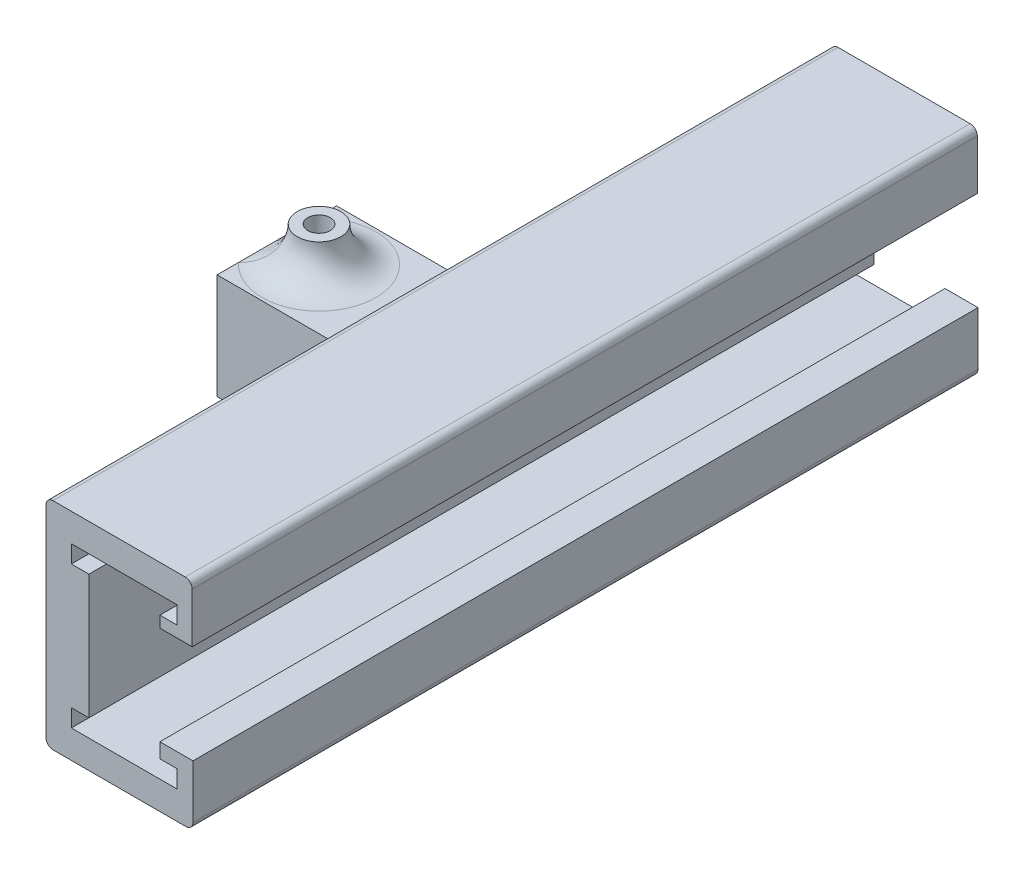
SolidWorks part; units mm, degrees
ref_plane "Front Plane" through (0, 0, 0) normal (0, 0, 1) x (1, 0, 0)
ref_plane "Top Plane" through (0, 0, 0) normal (0, 1, 0) x (1, 0, 0)
ref_plane "Right Plane" through (0, 0, 0) normal (1, 0, 0) x (0, 0, -1)
sketch "Sketch1" plane through (0, 0, 0) normal (0, 0, 1) x (1, 0, 0)
  line L0 (0, 0) -> (0, -2)
  line L1 (10.1, -2) -> (12.9, -2)
  line L2 (14.1, -0.8) -> (14.1, 4.1)
  line L3 (0, 0) -> (-2.1, 0)
  line L4 (-2.1, 0) -> (-2.1, 2.1)
  line L5 (-2.1, 2.1) -> (12.1, 2.1)
  line L6 (12.1, 2.1) -> (12.1, 0)
  line L7 (12.1, 0) -> (10.1, 0)
  line L8 (10.1, 0) -> (10.1, -2)
  line L9 (14.1, 4.1) -> (-4.1, 4.1)
  line L10 (-4.1, 4.1) -> (-4.1, -22.6)
  line L11 (0, -2) -> (0, -18.5)
  line L12 (0, -18.5) -> (-2.1, -18.5)
  line L13 (-2.1, -18.5) -> (-2.1, -20.6)
  line L14 (-2.1, -20.6) -> (12.2, -20.6)
  line L15 (12.2, -20.6) -> (12.2, -18.5)
  line L16 (12.2, -18.5) -> (10.1, -18.5)
  line L17 (10.1, -18.5) -> (10.1, -2)
  line L18 (-4.1, -22.6) -> (14.2, -22.6)
  line L19 (14.2, -22.6) -> (14.2, -17.7)
  line L20 (10.1, -16.5) -> (13, -16.5)
  line L21 (16.1, -2) -> (16.1, -1.9919)
  arc A0 (14.2, -17.7) -> (13, -16.5) centre (13, -17.7) ccw
  arc A1 (14.1, -0.8) -> (12.9, -2) centre (12.9, -0.8) cw
  point P27 (14.2, -16.5)
  dimension "D18" = 1.2
  dimension "D1" = 14.2
  dimension "D2" = 10.1
  dimension "D3" = 2.1
  dimension "D4" = 2.1
  dimension "D5" = 2
  dimension "D6" = 2
  dimension "D7" = 2
  dimension "D8" = 2
  dimension "D9" = 2
  dimension "D10" = 2
  dimension "D11" = 2.1
  dimension "D12" = 2.1
  dimension "D13" = 2.1
  dimension "D14" = 14.3
  dimension "D15" = 2
  dimension "D16" = 16.5
  dimension "D17" = 2
extrude "Boss-Extrude1" add sketch "Sketch1" along normal blind 85 contours L1 L21 L2 L9 L10 L18 L19 L20 L17 L16 L15 L14 L13 L12 L11 L0 L3 L4 L5 L6 L7 L8 region at (-0.3237, -1, 0)
sketch "Sketch2" plane through (14.1, 0, 0) normal (1, 0, 0) x (0, 0, -1)
  line L1 (-85, 4.1) -> (0, 4.1)
  line L2 (-85, 4.1) -> (-85, -11.9)
  line L3 (-85, -11.9) -> (0, -11.9)
  line L4 (0, 4.1) -> (0, -11.9)
  line L5 (0, -0.8) -> (0, 4.1) construction
  dimension "D1" = 16
extrude "Boss-Extrude2" add sketch "Sketch2" against normal blind 1.8
sketch "Sketch3" plane through (-4.1, 0, 0) normal (-1, 0, 0) x (0, 0, 1)
  line L0 (85, -22.6) -> (0, -22.6) construction
  line L1 (0, 4.1) -> (0, -22.6) construction
  circle A0 centre (42.5, -9.25) radius 4
  point P5 (42.5, -22.6)
  point P8 (0, -9.25)
  dimension "D1" = 8
extrude "Cut-Extrude1" cut sketch "Sketch3" against normal blind 10 contours A0 | A0 region at (-4.1, -9.25, 42.5)
sketch "Sketch4" plane through (0, 4.1, 0) normal (0, 1, 0) x (1, 0, 0)
  line L0 (14.1, 0) -> (-4.1, 0) construction
  line L1 (-4.1, -85) -> (-4.1, 0) construction
  line L2 (14.1, -85) -> (-4.1, -85) construction
  line L3 (0.9, -5) -> (0.9, -80) construction
  circle A0 centre (0.9, -5) radius 3
  circle A1 centre (0.9, -80) radius 3
  circle A2 centre (0.9, -5) radius 5
  circle A3 centre (0.9, -80) radius 5
  dimension "D1" = 6
  dimension "D2" = 6
  dimension "D3" = 2
extrude "Boss-Extrude3" add sketch "Sketch4" along normal blind 2
sketch "Sketch5" plane through (0, 4.1, 0) normal (0, 1, 0) x (1, 0, 0)
  line L0 (13.1, -40.3) -> (-0.9, -40.3)
  line L1 (-0.9, -40.3) -> (-0.9, -42.3)
  line L2 (-0.9, -42.3) -> (1.1, -42.3)
  line L3 (1.1, -42.3) -> (1.1, -46.8)
  line L4 (1.1, -46.8) -> (11.1, -46.8)
  line L5 (11.1, -46.8) -> (11.1, -42.3)
  line L6 (11.1, -42.3) -> (13.1, -42.3)
  line L7 (13.1, -42.3) -> (13.1, -40.3)
  line L8 (14.1, -85) -> (14.1, 0) construction
  line L9 (14.1, -85) -> (0.9, -85) construction
  dimension "D1" = 85
  dimension "D2" = 85
  dimension "D3" = 1
  dimension "D4" = 3
  dimension "D5" = 13
  dimension "D6" = 15
  dimension "D7" = 38.2
  dimension "D8" = 42.7
  dimension "D9" = 42.7
  dimension "D10" = 44.7
extrude "Boss-Extrude4" add sketch "Sketch5" along normal blind 50
sketch "Sketch6" plane through (11.1, 0, 0) normal (1, 0, 0) x (0, 0, -1)
  line L0 (-46.8, 54.1) -> (-46.8, 4.1) construction
  line L1 (-46.8, 54.1) -> (-46.8, 4.1)
  line L2 (-44.8, 4.1) -> (-46.8, 4.1)
  line L3 (-44.8, 6.5) -> (-44.8, 5.6)
  line L4 (-44.8, 5.6) -> (-46.1454, 5.2861)
  line L5 (-46.1454, 4.4139) -> (-44.8, 4.1)
  line L6 (-85, 4.1) -> (0, 4.1) construction
  line L8 (-46.3, 4.6087) -> (-46.3, 5.0913)
  line L9 (-44.8, 6.5) -> (-46.1454, 6.8139)
  line L10 (-46.3, 7.0087) -> (-46.3, 7.4913)
  line L11 (-46.1454, 7.6861) -> (-44.8, 8)
  line L12 (-44.8, 8.9) -> (-46.1454, 9.2139)
  line L13 (-46.3, 9.4087) -> (-46.3, 9.8913)
  line L14 (-46.1454, 10.0861) -> (-44.8, 10.4)
  line L15 (-44.8, 8.9) -> (-44.8, 8)
  line L16 (-44.8, 11.3) -> (-46.1454, 11.6139)
  line L17 (-46.3, 11.8087) -> (-46.3, 12.2913)
  line L18 (-46.1454, 12.4861) -> (-44.8, 12.8)
  line L19 (-44.8, 11.3) -> (-44.8, 10.4)
  line L20 (-44.8, 13.7) -> (-46.1454, 14.0139)
  line L21 (-46.3, 14.2087) -> (-46.3, 14.6913)
  line L22 (-46.1454, 14.8861) -> (-44.8, 15.2)
  line L23 (-44.8, 13.7) -> (-44.8, 12.8)
  line L24 (-44.8, 16.1) -> (-46.1454, 16.4139)
  line L25 (-46.3, 16.6087) -> (-46.3, 17.0913)
  line L26 (-46.1454, 17.2861) -> (-44.8, 17.6)
  line L27 (-44.8, 16.1) -> (-44.8, 15.2)
  line L28 (-44.8, 18.5) -> (-46.1454, 18.8139)
  line L29 (-46.3, 19.0087) -> (-46.3, 19.4913)
  line L30 (-46.1454, 19.6861) -> (-44.8, 20)
  line L31 (-44.8, 18.5) -> (-44.8, 17.6)
  line L32 (-44.8, 20.9) -> (-46.1454, 21.2139)
  line L33 (-46.3, 21.4087) -> (-46.3, 21.8913)
  line L34 (-46.1454, 22.0861) -> (-44.8, 22.4)
  line L35 (-44.8, 20.9) -> (-44.8, 20)
  line L36 (-44.8, 23.3) -> (-46.1454, 23.6139)
  line L37 (-46.3, 23.8087) -> (-46.3, 24.2913)
  line L38 (-46.1454, 24.4861) -> (-44.8, 24.8)
  line L39 (-44.8, 23.3) -> (-44.8, 22.4)
  line L40 (-44.8, 25.7) -> (-46.1454, 26.0139)
  line L41 (-46.3, 26.2087) -> (-46.3, 26.6913)
  line L42 (-46.1454, 26.8861) -> (-44.8, 27.2)
  line L43 (-44.8, 25.7) -> (-44.8, 24.8)
  line L44 (-44.8, 28.1) -> (-46.1454, 28.4139)
  line L45 (-46.3, 28.6087) -> (-46.3, 29.0913)
  line L46 (-46.1454, 29.2861) -> (-44.8, 29.6)
  line L47 (-44.8, 28.1) -> (-44.8, 27.2)
  line L48 (-44.8, 30.5) -> (-46.1454, 30.8139)
  line L49 (-46.3, 31.0087) -> (-46.3, 31.4913)
  line L50 (-46.1454, 31.6861) -> (-44.8, 32)
  line L51 (-44.8, 30.5) -> (-44.8, 29.6)
  line L52 (-44.8, 32.9) -> (-46.1454, 33.2139)
  line L53 (-46.3, 33.4087) -> (-46.3, 33.8913)
  line L54 (-46.1454, 34.0861) -> (-44.8, 34.4)
  line L55 (-44.8, 32.9) -> (-44.8, 32)
  line L56 (-44.8, 35.3) -> (-46.1454, 35.6139)
  line L57 (-46.3, 35.8087) -> (-46.3, 36.2913)
  line L58 (-46.1454, 36.4861) -> (-44.8, 36.8)
  line L59 (-44.8, 35.3) -> (-44.8, 34.4)
  line L60 (-44.8, 37.7) -> (-46.1454, 38.0139)
  line L61 (-46.3, 38.2087) -> (-46.3, 38.6913)
  line L62 (-46.1454, 38.8861) -> (-44.8, 39.2)
  line L63 (-44.8, 37.7) -> (-44.8, 36.8)
  line L64 (-44.8, 40.1) -> (-46.1454, 40.4139)
  line L65 (-46.3, 40.6087) -> (-46.3, 41.0913)
  line L66 (-46.1454, 41.2861) -> (-44.8, 41.6)
  line L67 (-44.8, 40.1) -> (-44.8, 39.2)
  line L68 (-44.8, 42.5) -> (-46.1454, 42.8139)
  line L69 (-46.3, 43.0087) -> (-46.3, 43.4913)
  line L70 (-46.1454, 43.6861) -> (-44.8, 44)
  line L71 (-44.8, 42.5) -> (-44.8, 41.6)
  line L72 (-44.8, 44.9) -> (-46.1454, 45.2139)
  line L73 (-46.3, 45.4087) -> (-46.3, 45.8913)
  line L74 (-46.1454, 46.0861) -> (-44.8, 46.4)
  line L75 (-44.8, 44.9) -> (-44.8, 44)
  line L76 (-44.8, 47.3) -> (-46.1454, 47.6139)
  line L77 (-46.3, 47.8087) -> (-46.3, 48.2913)
  line L78 (-46.1454, 48.4861) -> (-44.8, 48.8)
  line L79 (-44.8, 47.3) -> (-44.8, 46.4)
  line L80 (-44.8, 49.7) -> (-46.1454, 50.0139)
  line L81 (-46.3, 50.2087) -> (-46.3, 50.6913)
  line L82 (-46.1454, 50.8861) -> (-44.8, 51.2)
  line L83 (-44.8, 49.7) -> (-44.8, 48.8)
  line L84 (-44.8, 52.1) -> (-46.1454, 52.4139)
  line L85 (-46.3, 52.6087) -> (-46.3, 53.0913)
  line L86 (-46.1454, 53.2861) -> (-44.8, 53.6)
  line L87 (-44.8, 52.1) -> (-44.8, 51.2)
  line L88 (-46.8, 4.1) -> (-42.3, 4.1) construction
  line L89 (-42.3, 54.1) -> (-42.3, 4.1) construction
  line L91 (-44.8, 54.1) -> (-44.8, 53.6)
  line L92 (-46.8, 54.1) -> (-44.8, 54.1)
  line L93 (-46.8, 54.1) -> (-42.3, 54.1) construction
  line L95 (-44.8, 54.5) -> (-46.1454, 54.8139) [skipped]
  line L96 (-46.3, 55.0087) -> (-46.3, 55.4913) [skipped]
  line L97 (-46.1454, 55.6861) -> (-44.8, 56) [skipped]
  spline S0 degree 2 poles (-46.1454, 4.4139) (-46.2906, 4.4575) (-46.3, 4.6087) knots 0 0 0 1 1 1
  spline S1 degree 2 poles (-46.3, 5.0913) (-46.2906, 5.2425) (-46.1454, 5.2861) knots 0 0 0 1 1 1
  spline S2 degree 2 poles (-46.1454, 6.8139) (-46.2906, 6.8575) (-46.3, 7.0087) knots 0 0 0 1 1 1
  spline S3 degree 2 poles (-46.3, 7.4913) (-46.2906, 7.6425) (-46.1454, 7.6861) knots 0 0 0 1 1 1
  spline S4 degree 2 poles (-46.1454, 9.2139) (-46.2906, 9.2575) (-46.3, 9.4087) knots 0 0 0 1 1 1
  spline S5 degree 2 poles (-46.3, 9.8913) (-46.2906, 10.0425) (-46.1454, 10.0861) knots 0 0 0 1 1 1
  spline S6 degree 2 poles (-46.1454, 11.6139) (-46.2906, 11.6575) (-46.3, 11.8087) knots 0 0 0 1 1 1
  spline S7 degree 2 poles (-46.3, 12.2913) (-46.2906, 12.4425) (-46.1454, 12.4861) knots 0 0 0 1 1 1
  spline S8 degree 2 poles (-46.1454, 14.0139) (-46.2906, 14.0575) (-46.3, 14.2087) knots 0 0 0 1 1 1
  spline S9 degree 2 poles (-46.3, 14.6913) (-46.2906, 14.8425) (-46.1454, 14.8861) knots 0 0 0 1 1 1
  spline S10 degree 2 poles (-46.1454, 16.4139) (-46.2906, 16.4575) (-46.3, 16.6087) knots 0 0 0 1 1 1
  spline S11 degree 2 poles (-46.3, 17.0913) (-46.2906, 17.2425) (-46.1454, 17.2861) knots 0 0 0 1 1 1
  spline S12 degree 2 poles (-46.1454, 18.8139) (-46.2906, 18.8575) (-46.3, 19.0087) knots 0 0 0 1 1 1
  spline S13 degree 2 poles (-46.3, 19.4913) (-46.2906, 19.6425) (-46.1454, 19.6861) knots 0 0 0 1 1 1
  spline S14 degree 2 poles (-46.1454, 21.2139) (-46.2906, 21.2575) (-46.3, 21.4087) knots 0 0 0 1 1 1
  spline S15 degree 2 poles (-46.3, 21.8913) (-46.2906, 22.0425) (-46.1454, 22.0861) knots 0 0 0 1 1 1
  spline S16 degree 2 poles (-46.1454, 23.6139) (-46.2906, 23.6575) (-46.3, 23.8087) knots 0 0 0 1 1 1
  spline S17 degree 2 poles (-46.3, 24.2913) (-46.2906, 24.4425) (-46.1454, 24.4861) knots 0 0 0 1 1 1
  spline S18 degree 2 poles (-46.1454, 26.0139) (-46.2906, 26.0575) (-46.3, 26.2087) knots 0 0 0 1 1 1
  spline S19 degree 2 poles (-46.3, 26.6913) (-46.2906, 26.8425) (-46.1454, 26.8861) knots 0 0 0 1 1 1
  spline S20 degree 2 poles (-46.1454, 28.4139) (-46.2906, 28.4575) (-46.3, 28.6087) knots 0 0 0 1 1 1
  spline S21 degree 2 poles (-46.3, 29.0913) (-46.2906, 29.2425) (-46.1454, 29.2861) knots 0 0 0 1 1 1
  spline S22 degree 3 poles (-46.1454, 30.8139) (-46.2422, 30.8429) (-46.2937, 30.9079) (-46.3, 31.0087) knots 0 0 0 0 1 1 1 1
  spline S23 degree 2 poles (-46.3, 31.4913) (-46.2906, 31.6425) (-46.1454, 31.6861) knots 0 0 0 1 1 1
  spline S24 degree 2 poles (-46.1454, 33.2139) (-46.2906, 33.2575) (-46.3, 33.4087) knots 0 0 0 1 1 1
  spline S25 degree 2 poles (-46.3, 33.8913) (-46.2906, 34.0425) (-46.1454, 34.0861) knots 0 0 0 1 1 1
  spline S26 degree 2 poles (-46.1454, 35.6139) (-46.2906, 35.6575) (-46.3, 35.8087) knots 0 0 0 1 1 1
  spline S27 degree 3 poles (-46.3, 36.2913) (-46.2937, 36.3921) (-46.2422, 36.4571) (-46.1454, 36.4861) knots 0 0 0 0 1 1 1 1
  spline S28 degree 2 poles (-46.1454, 38.0139) (-46.2906, 38.0575) (-46.3, 38.2087) knots 0 0 0 1 1 1
  spline S29 degree 2 poles (-46.3, 38.6913) (-46.2906, 38.8425) (-46.1454, 38.8861) knots 0 0 0 1 1 1
  spline S30 degree 2 poles (-46.1454, 40.4139) (-46.2906, 40.4575) (-46.3, 40.6087) knots 0 0 0 1 1 1
  spline S31 degree 2 poles (-46.3, 41.0913) (-46.2906, 41.2425) (-46.1454, 41.2861) knots 0 0 0 1 1 1
  spline S32 degree 2 poles (-46.1454, 42.8139) (-46.2906, 42.8575) (-46.3, 43.0087) knots 0 0 0 1 1 1
  spline S33 degree 2 poles (-46.3, 43.4913) (-46.2906, 43.6425) (-46.1454, 43.6861) knots 0 0 0 1 1 1
  spline S34 degree 2 poles (-46.1454, 45.2139) (-46.2906, 45.2575) (-46.3, 45.4087) knots 0 0 0 1 1 1
  spline S35 degree 2 poles (-46.3, 45.8913) (-46.2906, 46.0425) (-46.1454, 46.0861) knots 0 0 0 1 1 1
  spline S36 degree 2 poles (-46.1454, 47.6139) (-46.2906, 47.6575) (-46.3, 47.8087) knots 0 0 0 1 1 1
  spline S37 degree 2 poles (-46.3, 48.2913) (-46.2906, 48.4425) (-46.1454, 48.4861) knots 0 0 0 1 1 1
  spline S38 degree 2 poles (-46.1454, 50.0139) (-46.2906, 50.0575) (-46.3, 50.2087) knots 0 0 0 1 1 1
  spline S39 degree 2 poles (-46.3, 50.6913) (-46.2906, 50.8425) (-46.1454, 50.8861) knots 0 0 0 1 1 1
  spline S40 degree 2 poles (-46.1454, 52.4139) (-46.2906, 52.4575) (-46.3, 52.6087) knots 0 0 0 1 1 1
  spline S41 degree 2 poles (-46.3, 53.0913) (-46.2906, 53.2425) (-46.1454, 53.2861) knots 0 0 0 1 1 1
  dimension "D2" = 0.2675
  dimension "D60" = 0.1317
  dimension "D64" = 0.2486
  dimension "D1" = 21
  dimension "D3" = 0.1317
  dimension "D4" = 0.1243
  dimension "D5" = 0.1317
  dimension "D6" = 0.1317
  dimension "D7" = 0.1317
  dimension "D8" = 0.1317
  dimension "D9" = 0.1243
  dimension "D10" = 0.0704
  dimension "D11" = 0.1243
  dimension "D12" = 0.1317
  dimension "D13" = 0.1317
  dimension "D14" = 0.0704
  dimension "D15" = 0.1317
  dimension "D16" = 0.1317
  dimension "D17" = 0.1317
  dimension "D18" = 0.1317
  dimension "D19" = 0.1317
  dimension "D20" = 0.1317
  dimension "D21" = 0.1317
  dimension "D22" = 0.1317
  dimension "D23" = 0.1243
  dimension "D24" = 0.1317
  dimension "D25" = 0.1243
  dimension "D26" = 0.1317
  dimension "D27" = 3.9567
  dimension "D28" = 19.5844
  dimension "D29" = 20.3156
  dimension "D30" = 21.9844
  dimension "D31" = 22.7156
  dimension "D32" = 24.3844
  dimension "D33" = 25.1156
  dimension "D34" = 26.7844
  dimension "D35" = 27.5156
  dimension "D36" = 29.1844
  dimension "D37" = 29.9156
  dimension "D38" = 31.5844
  dimension "D39" = 32.3156
  dimension "D40" = 33.9844
  dimension "D41" = 34.7156
  dimension "D42" = 36.3844
  dimension "D43" = 37.1156
  dimension "D44" = 38.7844
  dimension "D45" = 39.5156
  dimension "D46" = 41.1844
  dimension "D47" = 41.9156
  dimension "D48" = 43.5844
  dimension "D49" = 44.3156
  dimension "D50" = 45.9844
  dimension "D51" = 46.7156
  dimension "D52" = 48.3844
  dimension "D53" = 49.1156
  dimension "D54" = 0.1317
  dimension "D55" = 0.1317
  dimension "D56" = 0.1317
  dimension "D57" = 0.1317
  dimension "D58" = 0.1317
  dimension "D59" = 0.1317
  dimension "D61" = 0.1317
  dimension "D62" = 0.1317
  dimension "D63" = 0.1317
  dimension "D65" = 0.1317
  dimension "D66" = 0.1317
  dimension "D67" = 0.1317
  dimension "D68" = 0.1317
  dimension "D69" = 0.1317
  dimension "D70" = 0.1317
  dimension "D71" = 0.1317
  dimension "D72" = 0.1317
  dimension "D73" = 0.1317
  dimension "D74" = 0.1317
  dimension "D75" = 0.1317
  dimension "D76" = 0.1317
  dimension "D77" = 0.1317
  dimension "D78" = 0.1317
  dimension "D79" = 0.1317
  dimension "D80" = 2.5
  dimension "D81" = 2.5
  dimension "D82" = 3.8454
  dimension "D83" = 3.8454
  dimension "D84" = 3.9567
  dimension "D85" = 4
  dimension "D86" = 4
  dimension "D87" = 0.3139
  dimension "D88" = 0.3844
  dimension "D89" = 0.5087
  dimension "D90" = 0.9913
  dimension "D91" = 1.1156
  dimension "D92" = 1.1861
  dimension "D93" = 1.5
  dimension "D94" = 2.4
  dimension "D95" = 2.7139
  dimension "D96" = 2.7844
  dimension "D97" = 2.9087
  dimension "D98" = 3.3913
  dimension "D99" = 3.5156
  dimension "D100" = 3.5861
  dimension "D101" = 3.9
  dimension "D102" = 0.1112
  dimension "D103" = 0.1317
  dimension "D104" = 0.1317
  dimension "D105" = 1.3454
extrude "Cut-Extrude2" cut sketch "Sketch6" against normal through all
sketch "Sketch7" plane through (11.1, 0, 0) normal (1, 0, 0) x (0, 0, -1)
  line L0 (-46.3, 4.6087) -> (-46.3, 4.1)
  line L1 (-85, 4.1) -> (0, 4.1) construction
  line L2 (-46.3, 4.1) -> (-44.8, 4.1)
  line L3 (-44.8, 4.1) -> (-42.3, 4.1) construction
  line L4 (-44.8, 4.1) -> (-46.3, 4.6087)
  dimension "D1" = 1.5
extrude "Boss-Extrude5" add sketch "Sketch7" against normal up to surface (10 mm away) up to face at (1.1, 29.0179, 45.6877)
sketch "Sketch8" plane through (0, 4.1, 0) normal (0, 1, 0) x (1, 0, 0)
  circle A0 centre (0.9, -5) radius 3 construction
  circle A1 centre (0.9, -80) radius 3 construction
  circle A2 centre (0.9, -5) radius 3
  circle A3 centre (0.9, -80) radius 3
extrude "Boss-Extrude6" add sketch "Sketch8" along normal blind 50
sketch "Sketch9" plane through (-4.1, 0, 0) normal (-1, 0, 0) x (0, 0, 1)
  line L0 (48.6, -4.15) -> (48.6, -14.35)
  line L5 (36.5, -4.25) -> (48.5, -4.25) construction
  line L6 (36.5, -4.25) -> (36.5, -14.25)
  line L7 (36.5, -14.25) -> (48.5, -14.25)
  line L8 (48.5, -4.25) -> (48.5, -14.25) construction
  line L9 (36.4, -14.35) -> (48.6, -14.35)
  line L10 (36.4, -4.15) -> (36.4, -14.35)
  line L11 (36.4, -4.15) -> (48.6, -4.15)
  line L12 (34.9, -2.65) -> (50.1, -2.65)
  line L13 (50.1, -2.65) -> (50.1, -15.85)
  line L14 (34.9, -15.85) -> (50.1, -15.85)
  line L15 (34.9, -2.65) -> (34.9, -15.85)
  line L16 (85, 4.1) -> (85, -22.6) construction
  line L17 (85, -22.6) -> (0, -22.6) construction
  dimension "D1" = 0.1
  dimension "D3" = 34.9
  dimension "D4" = 48.5
  dimension "D5" = 6.75
  dimension "D6" = 18.35
  dimension "D2" = 1.5
extrude "Boss-Extrude7" add sketch "Sketch9" along normal blind 20 contours L12 L15 L14 L13 L10 L11 L0 L9 region at (-4.1, -2.8513, 42.5)
sketch "Sketch10" plane through (0, -15.85, 0) normal (0, -1, 0) x (1, 0, 0)
  line L4 (-4.1, 34.9) -> (-4.1, 50.1)
  line L5 (-4.1, 50.1) -> (-24.1, 50.1)
  line L6 (-24.1, 50.1) -> (-24.1, 34.9)
  line L7 (-24.1, 34.9) -> (-4.1, 34.9)
  line L8 (-4.1, 34.9) -> (-4.1, 50.1)
  line L9 (-4.1, 50.1) -> (-24.1, 50.1)
  line L10 (-24.1, 50.1) -> (-24.1, 34.9)
  line L11 (-24.1, 34.9) -> (-4.1, 34.9)
  dimension "D1" = 0
extrude "Cut-Extrude3" cut sketch "Sketch10" against normal through all
sketch "Sketch11" plane through (-4.1, 0, 0) normal (-1, 0, 0) x (0, 0, 1)
  arc A0 (45.748, -14.7646) -> (39.252, -14.7646) centre (42.5, -9.25) ccw
  arc A1 (39.252, -14.7646) -> (45.748, -14.7646) centre (42.5, -14.65) ccw
  dimension "D1" = 6.5
  dimension "D2" = 12.8
extrude "Cut-Extrude4" cut sketch "Sketch11" against normal blind 1
sketch "Sketch12" plane through (-4.1, 0, 0) normal (-1, 0, 0) x (0, 0, 1)
  line L11 (80, 4.1) -> (5, 4.1) construction
  line L12 (35, 4.1) -> (50, 4.1)
  line L13 (35, 4.1) -> (35, -2.9)
  line L14 (35, -2.9) -> (50, -2.9)
  line L15 (50, 4.1) -> (50, -2.9)
  line L16 (85, -22.6) -> (0, -22.6) construction
  line L17 (35, -21.6) -> (50, -21.6)
  line L18 (35, -21.6) -> (35, -31.6)
  line L19 (35, -31.6) -> (50, -31.6)
  line L20 (50, -21.6) -> (50, -31.6)
  line L21 (0, 4.1) -> (0, -22.6) construction
  circle A0 centre (42.5, -28.7) radius 1.5
  circle A1 centre (42.5, -0.7) radius 1.5
  dimension "D1" = 3
  dimension "D2" = 3
  dimension "D3" = 1
  dimension "D4" = 10
  dimension "D5" = 15
  dimension "D6" = 35
  dimension "D7" = 7
extrude "Boss-Extrude8" add sketch "Sketch12" along normal blind 6.5
sketch "Sketch13" plane through (-10.6, 0, 0) normal (-1, 0, 0) x (0, 0, 1)
  line L0 (50, -31.6) -> (50, -21.6) construction
  line L1 (35, -21.6) -> (50, -21.6)
  line L2 (35, -21.6) -> (35, -26.6)
  line L3 (35, -26.6) -> (50, -26.6)
  line L4 (50, -21.6) -> (50, -26.6)
  dimension "D1" = 5
extrude "Cut-Extrude5" cut sketch "Sketch13" against normal blind 3
fillet "Fillet1" radius 5 2 edges at (-4.1, -22.6, 42.5) (-4.1, -21.6, 42.5)
sketch "Sketch14" plane through (0, 4.1, 0) normal (0, 1, 0) x (1, 0, 0)
  line L1 (-10.6, -35) -> (-4.1, -35)
  line L2 (-10.6, -35) -> (-10.6, -50)
  line L3 (-10.6, -50) -> (-4.1, -50)
  line L4 (-4.1, -35) -> (-4.1, -50)
extrude "Cut-Extrude6" cut sketch "Sketch14" against normal blind 3
sketch "Sketch15" plane through (0, 0, 0) normal (0, 0, -1) x (-1, 0, 0)
  line L0 (-14.1, 4.1) -> (-0.9, 4.1) construction
  line L1 (-14.1, -11.9) -> (-14.7, -11.9)
  line L2 (-14.1, -11.9) -> (-14.1, 4.1)
  line L3 (-14.1, 4.1) -> (-14.7, 4.1)
  line L4 (-14.7, -11.9) -> (-14.7, 4.1)
  line L5 (-14.2, -22.6) -> (-14.2, -17.7) construction
  line L6 (-14.2, -22.6) -> (-14.2, -17.7)
  line L7 (-14.2, -22.6) -> (-14.8, -22.6)
  line L8 (-14.8, -22.6) -> (-14.8, -16.5)
  line L9 (-14.8, -16.5) -> (-13, -16.5)
  line L10 (-12.3, -11.9) -> (-12.3, -2) construction
  line L11 (-10.1, -2) -> (-12.3, -2)
  line L12 (-10.1, -2) -> (-10.1, -3)
  line L13 (-10.1, -3) -> (-12.3, -3)
  line L14 (-12.3, -2) -> (-12.3, -3)
  line L16 (-10.1, -16.5) -> (-14.8, -16.5)
  line L17 (-10.1, -16.5) -> (-10.1, -15.5)
  line L18 (-10.1, -15.5) -> (-14.8, -15.5)
  line L19 (-14.8, -16.5) -> (-14.8, -15.5)
  arc A0 (-13, -16.5) -> (-14.2, -17.7) centre (-13, -17.7) ccw construction
  arc A1 (-13, -16.5) -> (-14.2, -17.7) centre (-13, -17.7) ccw
  line M8 (-14.1, 4.1) -> (-14.1, -11.9)
  line M10 (-12.3, -11.9) -> (-12.3, -2)
  line M11 (-12.3, -2) -> (-10.1, -2)
  line M25 (-10.1, -16.5) -> (-13, -16.5)
  arc M26 (-13, -16.5) -> (-14.2, -17.7) centre (-13, -17.7) ccw
  line M27 (-14.2, -17.7) -> (-14.2, -22.6)
  dimension "D1" = 0.6
  dimension "D2" = 0.6
  dimension "D3" = 1
  dimension "D4" = 1
extrude "Boss-Extrude9" add sketch "Sketch15" against normal up to surface (85 mm away) contours L4 L1 L3 M8 | L13 L12 M11 M10 | L19 L9 L17 L18 M25 | L9 L8 L7 M27 M26 region at (14.4, -3.9, 0) region at (14.4558, -19.3334, 0) region at (12.45, -16, 0) region at (11.2, -2.5, 0) up to face at (6.9895, -9.2563, 85)
sketch "Sketch16" plane through (0, 0, 0) normal (0, 0, -1) x (-1, 0, 0)
  line L0 (-12.1, 0) -> (-10.1, 0) construction
  line L1 (-12.5, -0.4) -> (2.5, -0.4)
  line L2 (-12.5, -0.4) -> (-12.5, 2.1)
  line L3 (-12.5, 2.1) -> (2.5, 2.1)
  line L4 (2.5, -0.4) -> (2.5, 2.1)
  line L5 (-12.1, 2.1) -> (-12.1, 0) construction
  line L6 (0, 0) -> (2.1, 0) construction
  line L7 (2.1, 0) -> (2.1, 2.1) construction
  line L9 (2.1, 2.1) -> (-12.1, 2.1) construction
  line L10 (-10.1, -18.1) -> (-10.1, -0.4) construction
  line L11 (-10.1, 0) -> (-10.1, -3) construction
  line L12 (-10.1, -9.25) -> (-5.1, -9.25) construction
  line L13 (-12.2, -18.5) -> (-10.1, -18.5) construction
  line L14 (-12.5, -20.6) -> (2.5, -20.6)
  line L15 (2.5, -18.1) -> (2.5, -20.6)
  line L16 (-12.5, -18.1) -> (2.5, -18.1)
  line L17 (-12.5, -18.1) -> (-12.5, -20.6)
  dimension "D1" = 0.4
  dimension "D2" = 0.4
  dimension "D3" = 0.4
  dimension "D4" = 0.4
  dimension "D5" = 5
  dimension "D6" = 0.4
extrude "Cut-Extrude7" cut sketch "Sketch16" against normal through all
sketch "Sketch17" plane through (14.7, 0, 0) normal (1, 0, 0) x (0, 0, -1)
  circle A0 centre (-42.5, -9.25) radius 5
  dimension "D1" = 10
extrude "Cut-Extrude8" cut sketch "Sketch17" against normal blind 10 and the other way blind 10
sketch "Sketch18" plane through (0, 54.1, 0) normal (0, 1, 0) x (1, 0, 0)
  circle A0 centre (0.9, -5) radius 3 construction
  circle A1 centre (0.9, -80) radius 3 construction
  circle A2 centre (0.9, -5) radius 3
  circle A3 centre (0.9, -80) radius 3
  circle A4 centre (0.9, -5) radius 2.9
  circle A5 centre (0.9, -80) radius 2.9
  dimension "D1" = 0.1
extrude "Cut-Extrude9" cut sketch "Sketch18" against normal up to surface (48 mm away) up to face at (-4.1, 6.1, 80)
sketch "Sketch19" plane through (0, 0, 85) normal (0, 0, 1) x (1, 0, 0)
  line L0 (14.7, -11.9) -> (14.7, 4.1) construction
  line L1 (12.3, -11.9) -> (14.7, -11.9)
  line L2 (12.3, -11.9) -> (12.3, -9.9)
  line L3 (12.3, -9.9) -> (14.7, -9.9)
  line L4 (14.7, -11.9) -> (14.7, -9.9)
  dimension "D1" = 2
extrude "Cut-Extrude10" cut sketch "Sketch19" against normal through all
sketch "Sketch20" plane through (0, 0, 85) normal (0, 0, 1) x (1, 0, 0)
  line L0 (14.8, -22.6) -> (14.8, -15.5) construction
  line L1 (10.1, -15.5) -> (14.8, -15.5)
  line L2 (10.1, -15.5) -> (10.1, -16)
  line L3 (10.1, -16) -> (14.8, -16)
  line L4 (14.8, -15.5) -> (14.8, -16)
  dimension "D1" = 0.5
extrude "Cut-Extrude11" cut sketch "Sketch20" against normal through all
sketch "Sketch21" plane through (0, 54.1, 0) normal (0, 1, 0) x (1, 0, 0)
  circle A0 centre (0.9, -80) radius 3
  circle A1 centre (0.9, -5) radius 3
  dimension "D1" = 6
  dimension "D2" = 6
extrude "Boss-Extrude10" add sketch "Sketch21" against normal up to surface (48 mm away) up to face at (-4.1, 6.1, 80)
sketch "Sketch22" plane through (0, 0, 85) normal (0, 0, 1) x (1, 0, 0)
  line L1 (-4.1, 4.1) -> (14.8, 4.1)
  line L2 (-4.1, 4.1) -> (-4.1, -22.6)
  line L3 (-4.1, -22.6) -> (14.8, -22.6)
  line L4 (14.8, 4.1) -> (14.8, -22.6)
extrude "Cut-Extrude12" cut sketch "Sketch22" against normal through all flip side to cut
sketch "Sketch23" plane through (-3.1, 0, 0) normal (-1, 0, 0) x (0, 0, 1)
  circle A0 centre (42.5, -9.25) radius 4 construction
  circle A1 centre (42.5, -9.25) radius 4
  arc A2 (39.252, -14.7646) -> (45.748, -14.7646) centre (42.5, -14.65) ccw
  arc A3 (45.748, -14.7646) -> (39.252, -14.7646) centre (42.5, -9.25) ccw
  arc A4 (39.252, -14.7646) -> (45.748, -14.7646) centre (42.5, -14.65) ccw
  arc A5 (45.748, -14.7646) -> (39.252, -14.7646) centre (42.5, -9.25) ccw
  dimension "D1" = 0
extrude "Boss-Extrude11" add sketch "Sketch23" along normal up to surface (1 mm away) up to face at (-4.1, -10.375, 42.5)
sketch "Sketch24" plane through (-4.1, 0, 0) normal (-1, 0, 0) x (0, 0, 1)
  line L0 (36, -14.75) -> (36, -3.75)
  line L1 (36.5, -14.25) -> (48.5, -14.25) construction
  line L2 (36.5, -14.25) -> (36.5, -4.25) construction
  line L3 (36.5, -4.25) -> (48.5, -4.25) construction
  line L4 (48.5, -14.25) -> (48.5, -4.25) construction
  line L5 (36.5, -14.25) -> (48.5, -4.25) construction
  line L6 (36.5, -4.25) -> (48.5, -14.25) construction
  line L7 (36, -3.75) -> (49, -3.75)
  line L8 (49, -14.75) -> (49, -3.75)
  line L9 (36, -14.75) -> (49, -14.75)
  line L10 (34, -1.75) -> (51, -1.75)
  line L11 (51, -16.75) -> (51, -1.75)
  line L12 (34, -16.75) -> (51, -16.75)
  line L13 (34, -16.75) -> (34, -1.75)
  point P0 (42.5, -9.25)
  dimension "D1" = 12
  dimension "D2" = 10
  dimension "D3" = 0.5
  dimension "D4" = 2
extrude "Boss-Extrude12" add sketch "Sketch24" along normal blind 25
sketch "Sketch25" plane through (0, -1.75, 0) normal (0, 1, 0) x (1, 0, 0)
  line L0 (-29.1, -51) -> (-29.1, -34) construction
  circle A0 centre (-23.1, -42.5) radius 1.6
  circle A1 centre (-23.1, -42.5) radius 3.1
  point P4 (-29.1, -42.5)
  dimension "D1" = 3.2
  dimension "D3" = 6.2
  dimension "D2" = 6
extrude "Boss-Extrude13" add sketch "Sketch25" along normal blind 5
sketch "Sketch26" plane through (0, -1.75, 0) normal (0, 1, 0) x (1, 0, 0)
  circle A1 centre (-23.1, -42.5) radius 1.6
  circle A2 centre (-23.1, -42.5) radius 1.6
  dimension "D1" = 0
extrude "Cut-Extrude13" cut sketch "Sketch26" against normal blind 5
fillet "Fillet2" radius 5 1 edges at (-20, -1.75, 42.5)
fillet "Fillet3" radius 5 4 edges at (-4.1, -9.25, 51) (-4.1, -16.75, 42.5) (-4.1, -9.25, 34) (-4.1, -1.75, 42.5)
sketch "Sketch27" plane through (0, 0, 0) normal (0, 0, -1) x (-1, 0, 0)
  line L0 (-12.3, -9.9) -> (-12.3, -3) construction
  line L1 (-14.7, -9.9) -> (-12.3, -9.9)
  line L2 (-14.7, -9.9) -> (-14.7, -3)
  line L3 (-14.7, -3) -> (-12.3, -3)
  line L4 (-12.3, -9.9) -> (-12.3, -3)
  line L5 (-10.1, -3) -> (-12.3, -3) construction
extrude "Cut-Extrude14" cut sketch "Sketch27" against normal through all
sketch "Sketch28" plane through (0, 0, 0) normal (0, 0, -1) x (-1, 0, 0)
  line L0 (-14.7, 4.1) -> (-14.7, 5.1)
  line L1 (-13.7, 6.1) -> (5.1, 6.1)
  line L2 (6.1, 5.1) -> (6.1, -23.6)
  line L3 (5.1, -24.6) -> (-13.8, -24.6)
  line L4 (-14.8, -23.6) -> (-14.8, -22.6)
  line L5 (-14.7, 4.1) -> (4.1, 4.1) construction
  line L6 (4.1, 4.1) -> (4.1, -22.6) construction
  line L7 (4.1, -21.75) -> (4.1, 3.25) construction
  line L8 (4.1, -22.6) -> (-14.8, -22.6) construction
  line L9 (-14.7, 4.1) -> (4.1, 4.1)
  line L10 (4.1, 4.1) -> (4.1, -22.6)
  line L11 (4.1, -21.75) -> (4.1, 3.25)
  line L12 (4.1, -22.6) -> (-14.8, -22.6)
  arc A0 (-13.8, -24.6) -> (-14.8, -23.6) centre (-13.8, -23.6) cw
  arc A1 (6.1, -23.6) -> (5.1, -24.6) centre (5.1, -23.6) cw
  arc A2 (5.1, 6.1) -> (6.1, 5.1) centre (5.1, 5.1) cw
  arc A3 (-14.7, 5.1) -> (-13.7, 6.1) centre (-13.7, 5.1) cw
  dimension "D4" = 1
  dimension "D1" = 2
  dimension "D2" = 2
  dimension "D3" = 2
extrude "Boss-Extrude14" add sketch "Sketch28" against normal up to surface (85 mm away) contours L1 A2 L2 A1 L3 A0 L4 L12 L10 L9 L0 A3 up to face at (6.56, -9.3, 85)
sketch "Sketch29" plane through (0, 0, 85) normal (0, 0, 1) x (1, 0, 0)
  line L0 (14.7, -3) -> (14.7, 5.1) construction
  line L1 (10.1, -3) -> (14.7, -3)
  line L2 (10.1, -3) -> (10.1, -2)
  line L3 (10.1, -2) -> (14.7, -2)
  line L4 (14.7, -3) -> (14.7, -2)
  dimension "D1" = 1
extrude "Cut-Extrude15" cut sketch "Sketch29" against normal through all both and the other way through all
sketch "Sketch30" plane through (-4.1, 0, 0) normal (1, 0, 0) x (0, 0, -1)
  circle A1 centre (-42.5, -9.25) radius 4
  circle A2 centre (-42.5, -9.25) radius 4
  dimension "D1" = 0
extrude "Cut-Extrude16" cut sketch "Sketch30" against normal blind 10
scale "Escala1" scale about origin uniform scaling yes scale factor 1.5
sketch "Croquis1" plane through (0, 0, 127.5) normal (0, 0, 1) x (1, 0, 0)
  line L20 (15.15, -3) -> (22.05, -3)
  line L21 (22.05, -3) -> (22.05, 7.65)
  line L22 (20.55, 9.15) -> (-7.65, 9.15)
  line L23 (-9.15, 7.65) -> (-9.15, -35.4)
  line L24 (-7.65, -36.9) -> (20.7, -36.9)
  line L25 (22.2, -35.4) -> (22.2, -24)
  line L26 (22.2, -24) -> (15.15, -24)
  line L27 (15.15, -24) -> (15.15, -27.15)
  line L28 (15.15, -27.15) -> (18.75, -27.15)
  line L29 (18.75, -27.15) -> (18.75, -30.9)
  line L30 (18.75, -30.9) -> (-3.75, -30.9)
  line L31 (-3.75, -30.9) -> (-3.75, -27.15)
  line L32 (-3.75, -27.15) -> (0, -27.15)
  line L33 (0, -27.15) -> (0, -0.6)
  line L34 (0, -0.6) -> (-3.75, -0.6)
  line L35 (-3.75, -0.6) -> (-3.75, 3.15)
  line L36 (-3.75, 3.15) -> (18.75, 3.15)
  line L37 (18.75, 3.15) -> (18.75, -0.6)
  line L38 (18.75, -0.6) -> (15.15, -0.6)
  line L39 (15.15, -0.6) -> (15.15, -3)
  line L40 (15.15, -3) -> (22.05, -3)
  line L41 (22.05, -3) -> (22.05, 7.65)
  line L42 (20.55, 9.15) -> (-7.65, 9.15)
  line L43 (-9.15, 7.65) -> (-9.15, -35.4)
  line L44 (-7.65, -36.9) -> (20.7, -36.9)
  line L45 (22.2, -35.4) -> (22.2, -24)
  line L46 (22.2, -24) -> (15.15, -24)
  line L47 (15.15, -24) -> (15.15, -27.15)
  line L48 (15.15, -27.15) -> (18.75, -27.15)
  line L49 (18.75, -27.15) -> (18.75, -30.9)
  line L50 (18.75, -30.9) -> (-3.75, -30.9)
  line L51 (-3.75, -30.9) -> (-3.75, -27.15)
  line L52 (-3.75, -27.15) -> (0, -27.15)
  line L53 (0, -27.15) -> (0, -0.6)
  line L54 (0, -0.6) -> (-3.75, -0.6)
  line L55 (-3.75, -0.6) -> (-3.75, 3.15)
  line L56 (-3.75, 3.15) -> (18.75, 3.15)
  line L57 (18.75, 3.15) -> (18.75, -0.6)
  line L58 (18.75, -0.6) -> (15.15, -0.6)
  line L59 (15.15, -0.6) -> (15.15, -3)
  arc A4 (22.05, 7.65) -> (20.55, 9.15) centre (20.55, 7.65) ccw
  arc A5 (-7.65, 9.15) -> (-9.15, 7.65) centre (-7.65, 7.65) ccw
  arc A6 (-9.15, -35.4) -> (-7.65, -36.9) centre (-7.65, -35.4) ccw
  arc A7 (20.7, -36.9) -> (22.2, -35.4) centre (20.7, -35.4) ccw
  arc A8 (22.05, 7.65) -> (20.55, 9.15) centre (20.55, 7.65) ccw
  arc A9 (-7.65, 9.15) -> (-9.15, 7.65) centre (-7.65, 7.65) ccw
  arc A10 (-9.15, -35.4) -> (-7.65, -36.9) centre (-7.65, -35.4) ccw
  arc A11 (20.7, -36.9) -> (22.2, -35.4) centre (20.7, -35.4) ccw
  dimension "D1" = 0
extrude "Saliente-Extruir1" add sketch "Croquis1" along normal blind 20
sketch "Croquis2" plane through (0, 0, 0) normal (0, 0, -1) x (-1, 0, 0)
  line L20 (-22.05, 7.65) -> (-22.05, -3)
  line L21 (-22.05, -3) -> (-15.15, -3)
  line L22 (-15.15, -3) -> (-15.15, -0.6)
  line L23 (-15.15, -0.6) -> (-18.75, -0.6)
  line L24 (-18.75, -0.6) -> (-18.75, 3.15)
  line L25 (-18.75, 3.15) -> (3.75, 3.15)
  line L26 (3.75, 3.15) -> (3.75, -0.6)
  line L27 (3.75, -0.6) -> (0, -0.6)
  line L28 (0, -0.6) -> (0, -27.15)
  line L29 (0, -27.15) -> (3.75, -27.15)
  line L30 (3.75, -27.15) -> (3.75, -30.9)
  line L31 (3.75, -30.9) -> (-18.75, -30.9)
  line L32 (-18.75, -30.9) -> (-18.75, -27.15)
  line L33 (-18.75, -27.15) -> (-15.15, -27.15)
  line L34 (-15.15, -27.15) -> (-15.15, -24)
  line L35 (-15.15, -24) -> (-22.2, -24)
  line L36 (-22.2, -24) -> (-22.2, -35.4)
  line L37 (-20.7, -36.9) -> (7.65, -36.9)
  line L38 (9.15, -35.4) -> (9.15, 7.65)
  line L39 (7.65, 9.15) -> (-20.55, 9.15)
  line L40 (-22.05, 7.65) -> (-22.05, -3)
  line L41 (-22.05, -3) -> (-15.15, -3)
  line L42 (-15.15, -3) -> (-15.15, -0.6)
  line L43 (-15.15, -0.6) -> (-18.75, -0.6)
  line L44 (-18.75, -0.6) -> (-18.75, 3.15)
  line L45 (-18.75, 3.15) -> (3.75, 3.15)
  line L46 (3.75, 3.15) -> (3.75, -0.6)
  line L47 (3.75, -0.6) -> (0, -0.6)
  line L48 (0, -0.6) -> (0, -27.15)
  line L49 (0, -27.15) -> (3.75, -27.15)
  line L50 (3.75, -27.15) -> (3.75, -30.9)
  line L51 (3.75, -30.9) -> (-18.75, -30.9)
  line L52 (-18.75, -30.9) -> (-18.75, -27.15)
  line L53 (-18.75, -27.15) -> (-15.15, -27.15)
  line L54 (-15.15, -27.15) -> (-15.15, -24)
  line L55 (-15.15, -24) -> (-22.2, -24)
  line L56 (-22.2, -24) -> (-22.2, -35.4)
  line L57 (-20.7, -36.9) -> (7.65, -36.9)
  line L58 (9.15, -35.4) -> (9.15, 7.65)
  line L59 (7.65, 9.15) -> (-20.55, 9.15)
  arc A4 (-22.2, -35.4) -> (-20.7, -36.9) centre (-20.7, -35.4) ccw
  arc A5 (7.65, -36.9) -> (9.15, -35.4) centre (7.65, -35.4) ccw
  arc A6 (9.15, 7.65) -> (7.65, 9.15) centre (7.65, 7.65) ccw
  arc A7 (-20.55, 9.15) -> (-22.05, 7.65) centre (-20.55, 7.65) ccw
  arc A8 (-22.2, -35.4) -> (-20.7, -36.9) centre (-20.7, -35.4) ccw
  arc A9 (7.65, -36.9) -> (9.15, -35.4) centre (7.65, -35.4) ccw
  arc A10 (9.15, 7.65) -> (7.65, 9.15) centre (7.65, 7.65) ccw
  arc A11 (-20.55, 9.15) -> (-22.05, 7.65) centre (-20.55, 7.65) ccw
  dimension "D1" = 0
extrude "Saliente-Extruir2" add sketch "Croquis2" along normal blind 20
